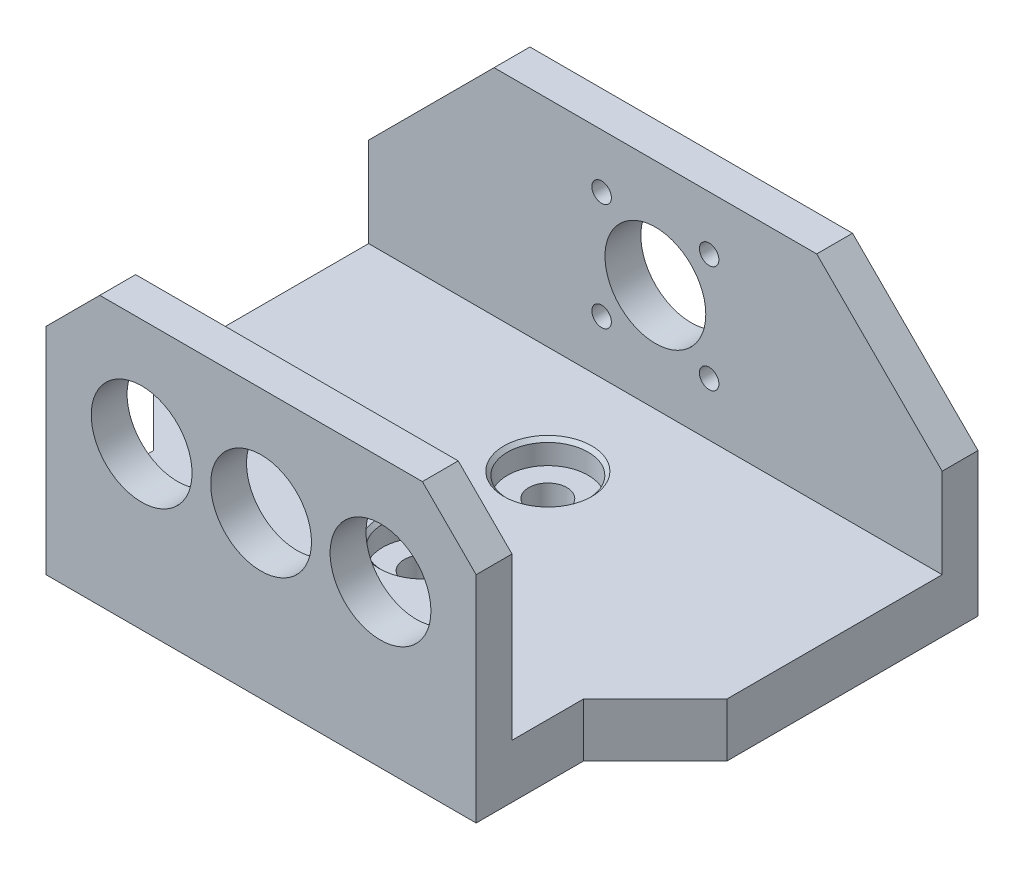
SolidWorks part; units mm, degrees
ref_plane "Front Plane" through (0, 0, 0) normal (0, 0, 1) x (1, 0, 0)
ref_plane "Top Plane" through (0, 0, 0) normal (0, 1, 0) x (1, 0, 0)
ref_plane "Right Plane" through (0, 0, 0) normal (1, 0, 0) x (0, 0, -1)
sketch "Sketch1" plane through (0, 0, 0) normal (0, 1, 0) x (1, 0, 0)
  line L1 (0, 0) -> (101.6, 0)
  line L2 (0, 0) -> (0, 76.2)
  line L3 (0, 76.2) -> (101.6, 76.2)
  line L4 (101.6, 0) -> (101.6, 76.2)
  dimension "D1" = 76.2
  dimension "D2" = 101.6
extrude "Boss-Extrude1" add sketch "Sketch1" along normal blind 50.8 contours L3 L4 L1 L2
ref_plane "Plane1" through (0, 0, -38.1) normal (0, 0, 1) x (1, 0, 0)
sketch "Sketch9" plane through (0, 0, -38.1) normal (0, 0, 1) x (1, 0, 0)
  line L0 (0, 50.8) -> (101.6, 50.8) construction
  line L1 (0, 50.8) -> (101.6, 50.8)
  line L2 (50.8, 50.8) -> (50.8, 0) construction
  line L3 (0, 50.8) -> (0, 9.525)
  line L4 (0, 9.525) -> (101.6, 9.525)
  line L5 (101.6, 50.8) -> (101.6, 9.525)
  line L6 (0, 0) -> (101.6, 0) construction
  line L7 (0, 0) -> (101.6, 0) construction
  point P8 (50.8, 9.525)
  dimension "D1" = 9.525
extrude "Cut-Extrude1" cut sketch "Sketch9" against normal blind 31.75 and the other way blind 31.75
hole_wizard "45/64 (0.70313) Diameter Hole1" positions "Sketch4" profile "Sketch5" hole size "45/64" standard "ANSI Inch" end condition through all
sketch "Sketch4" plane through (0, 0, 0) normal (0, 0, 1) x (1, 0, 0)
  line L1 (0, 28.5242) -> (101.6, 28.5242) construction
  line L2 (0, 50.8) -> (0, 0) construction
  line L3 (101.6, 50.8) -> (101.6, 0) construction
  line L5 (0, 9.525) -> (101.6, 9.525) construction
  line L6 (0, 9.525) -> (101.6, 9.525) construction
  point P7 (50.8, 28.5242)
  point P16 (50.8, 28.5242)
  dimension "D1" = 18.9992
sketch "Sketch5" plane through (50.8, 28.5242, 0) normal (1, 0, 0) x (0, -1, 0)
  line L0 (0, 0) -> (0, 76.2)
  line L1 (0, 76.2) -> (8.9298, 76.2)
  line L2 (8.9298, 76.2) -> (8.9298, 0)
  line L5 (8.9298, 0) -> (0, 0)
  line L11 (0, -6.35) -> (0, 107.95) construction
  dimension "Thru Hole Dia." = 17.8595
  dimension "Thru Hole Depth" = 76.2
hole_wizard "45/64 (0.70313) Diameter Hole2" positions "Sketch7" profile "Sketch6" hole size "45/64" standard "ANSI Inch"
sketch "Sketch7" plane through (0, 0, 0) normal (0, 0, 1) x (1, 0, 0)
  line L2 (0, 28.5242) -> (152.4, 28.5242) construction
  line L5 (50.8, 28.5242) -> (50.8, 0) construction
  line L6 (0, 0) -> (101.6, 0) construction
  circle A1 centre (50.8, 28.5242) radius 8.9298 construction
  point P0 (29.6418, 28.5242)
  point P2 (71.9582, 28.5242)
  dimension "D1" = 21.1582
  dimension "D2" = 21.1582
sketch "Sketch6" plane through (29.6418, 28.5242, 0) normal (1, 0, 0) x (0, -1, 0)
  line L0 (0, 0) -> (0, 30.7655)
  line L1 (0, 30.7655) -> (8.9298, 25.4)
  line L2 (8.9298, 25.4) -> (8.9298, 0)
  line L5 (8.9298, 0) -> (0, 0)
  line L10 (0, 30.7655) -> (-8.9298, 25.4) construction
  line L11 (0, -6.35) -> (0, 107.95) construction
  dimension "Hole Dia." = 17.8595
  dimension "Hole Depth" = 25.4
  dimension "Drill Angle" = 118
hole_wizard "CBORE for 1/4 Binding Head Machine Screw1" positions "Sketch13" profile "Sketch14" counterbore size "1/4" standard "ANSI Inch" end condition through all
sketch "Sketch13" plane through (0, 9.525, 0) normal (0, 1, 0) x (1, 0, 0)
  line L0 (50.8, 69.85) -> (50.8, 6.35) construction
  line L1 (0, 69.85) -> (101.6, 69.85) construction
  line L2 (0, 6.35) -> (101.6, 6.35) construction
  line L3 (0, 76.2) -> (101.6, 76.2) construction
  line L4 (0, 76.2) -> (101.6, 76.2) construction
  point P9 (50.8, 50.8)
  point P11 (50.8, 28.702)
  dimension "D1" = 22.098
  dimension "D2" = 25.4
sketch "Sketch14" plane through (50.8, 9.525, -50.8) normal (1, 0, 0) x (0, 0, 1)
  line L0 (0, 0) -> (0, 9.525)
  line L1 (0, 9.525) -> (3.3782, 9.525)
  line L3 (3.3782, 9.525) -> (3.3782, 4.191)
  line L4 (7.1437, 4.191) -> (3.3782, 4.191)
  line L5 (7.1437, 4.191) -> (7.1438, 0.635)
  line L6 (7.1438, 0.635) -> (7.7788, 0)
  line L7 (7.7788, 0) -> (0, 0)
  line L8 (-7.1438, 0.635) -> (-7.7788, 0) construction
  line L11 (0, -6.35) -> (0, 107.95) construction
  dimension "Thru Hole Dia." = 6.7564
  dimension "Thru Hole Depth" = 9.525
  dimension "C'Bore Dia." = 14.2875
  dimension "C'Bore Depth" = 4.191
  dimension "Near C'Sink Dia." = 15.5575
  dimension "Near C'Sink Angle" = 90
sketch "Sketch17" plane through (0, 0, 0) normal (0, 0, 1) x (1, 0, 0)
  line L0 (0, 25.4) -> (22.225, 47.625)
  line L1 (0, 50.8) -> (0, 0) construction
  line L2 (22.225, 47.625) -> (79.375, 47.625)
  line L3 (79.375, 47.625) -> (101.6, 25.4)
  line L4 (101.6, 50.8) -> (101.6, 0) construction
  line L5 (0, 25.4) -> (0, 50.8)
  line L6 (0, 50.8) -> (101.6, 50.8)
  line L7 (101.6, 50.8) -> (101.6, 25.4)
  dimension "D1" = 3.175
  dimension "D2" = 45
  dimension "D3" = 22.225
extrude "Cut-Extrude3" cut sketch "Sketch17" against normal through all
hole_wizard "#8-32 Tapped Hole1" positions "Sketch19" profile "Sketch20" tap size "#8-32" standard "ANSI Inch" end condition up to next
sketch "Sketch19" plane through (0, 0, -76.2) normal (0, 0, -1) x (-1, 0, 0)
  line L1 (-60.325, 18.9992) -> (-41.275, 18.9992) construction
  line L2 (-60.325, 18.9992) -> (-60.325, 38.0492) construction
  line L3 (-60.325, 38.0492) -> (-41.275, 38.0492) construction
  line L4 (-41.275, 18.9992) -> (-41.275, 38.0492) construction
  line L5 (-60.325, 18.9992) -> (-41.275, 38.0492) construction
  line L6 (-60.325, 38.0492) -> (-41.275, 18.9992) construction
  circle A0 centre (-50.8, 28.5242) radius 19.05 construction
  point P5 (-41.275, 38.0492)
  point P112 (-60.325, 18.9992)
  point P113 (-60.325, 38.0492)
  point P114 (-41.275, 18.9992)
  dimension "D1" = 38.1
  dimension "D2" = 19.05
sketch "Sketch20" plane through (41.275, 38.0492, -76.2) normal (1, 0, 0) x (0, 1, 0)
  line L0 (0, 0) -> (0, 6.35)
  line L1 (0, 6.35) -> (1.7272, 6.35)
  line L2 (1.7272, 6.35) -> (1.7272, 0)
  line L5 (1.7272, 0) -> (0, 0)
  line L11 (0, -6.35) -> (0, 107.95) construction
  dimension "Thru Tap Drill Dia." = 3.4544
  dimension "Thru Tap Drill Depth" = 6.35
cosmetic thread "Hole Thread1" parameters "D2"=4.1656
cosmetic thread "Hole Thread2" parameters "D2"=4.1656
cosmetic thread "Hole Thread3" parameters "D2"=4.1656
cosmetic thread "Hole Thread4" parameters "D2"=4.1656
sketch "Sketch21" plane through (0, 0, 0) normal (0, -1, 0) x (1, 0, 0)
  line L0 (50.8, 0) -> (50.8, -76.2) construction
  line L1 (0, 0) -> (101.6, 0) construction
  line L2 (0, -76.2) -> (101.6, -76.2) construction
  line L3 (0, 0) -> (0, -31.75)
  line L4 (0, 0) -> (0, -76.2) construction
  line L5 (0, -31.75) -> (12.7, -19.05)
  line L6 (12.7, -19.05) -> (12.7, 0)
  line L7 (12.7, 0) -> (0, 0)
  line L8 (88.9, 0) -> (101.6, 0)
  line L9 (88.9, -19.05) -> (88.9, 0)
  line L10 (101.6, -31.75) -> (88.9, -19.05)
  line L11 (101.6, 0) -> (101.6, -31.75)
  dimension "D1" = 45
  dimension "D2" = 12.7
  dimension "D3" = 31.75
extrude "Cut-Extrude4" cut sketch "Sketch21" against normal through all
